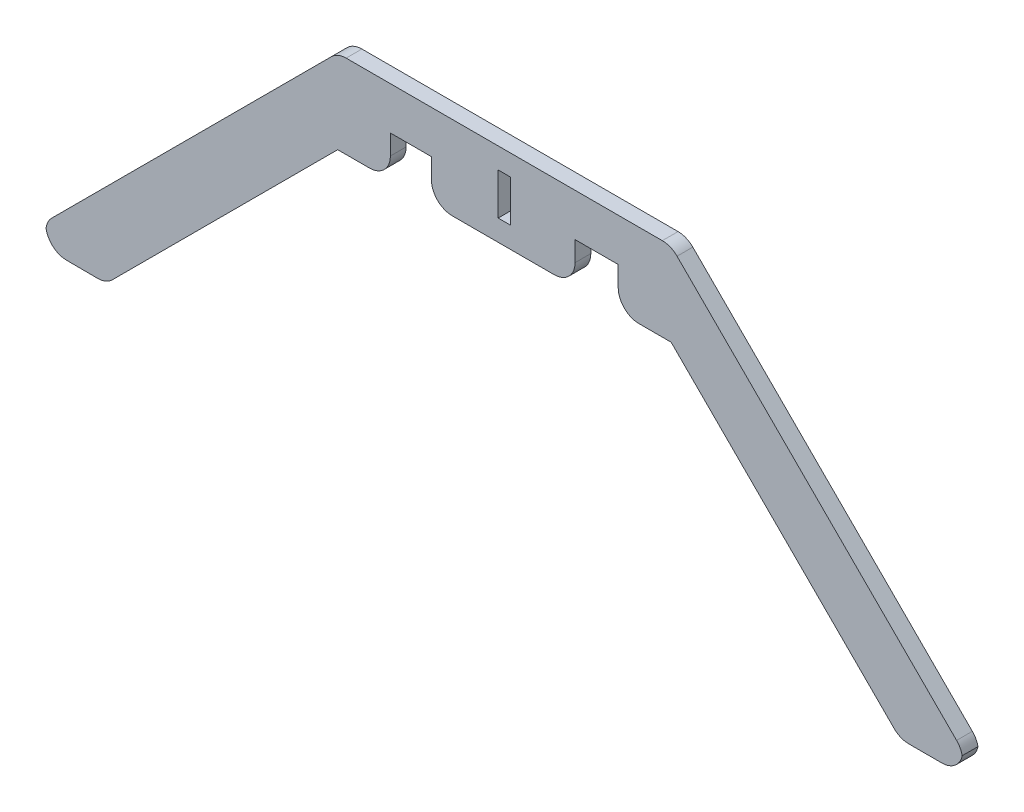
SolidWorks part; units mm, degrees
ref_plane "Front Plane" through (0, 0, 0) normal (0, 0, 1) x (1, 0, 0)
ref_plane "Top Plane" through (0, 0, 0) normal (0, 1, 0) x (1, 0, 0)
ref_plane "Right Plane" through (0, 0, 0) normal (1, 0, 0) x (0, 0, -1)
other "Center of Mass"
sketch "Sketch1" plane through (0, 0, 0) normal (0, 0, 1) x (1, 0, 0)
  line L1 (0, 0) -> (279.4, 0)
  line L2 (0, 0) -> (0, 254)
  line L3 (0, 254) -> (279.4, 254)
  line L4 (279.4, 0) -> (279.4, 254)
  line L5 (0, 0) -> (279.4, 254) construction
  line L6 (0, 254) -> (279.4, 0) construction
  point P4 (139.7, 127)
  dimension "D1" = 279.4
  dimension "D2" = 254
extrude "Boss-Extrude1" add sketch "Sketch1" along normal blind 4.8
ref_plane "Plane1" through (139.7, 0, 0) normal (-1, 0, 0) x (0, 0, 1)
sketch "Sketch4" plane through (0, 0, 0) normal (0, 0, -1) x (-1, 0, 0)
  line L16 (0.6384, 79.1893) -> (-88.9, 168.7277)
  line L17 (-88.9, 168.7277) -> (-190.5, 168.7277)
  line L18 (-190.5, 168.7277) -> (-279.4, 79.8277)
  line L20 (-18.4112, 72.7241) -> (-88.9574, 143.2703)
  line L21 (0.6384, 72.8393) -> (-18.4112, 72.7241)
  line L22 (-88.9574, 143.2703) -> (-190.5574, 143.2703)
  line L23 (-279.4, 73.4777) -> (-260.35, 73.4777)
  line L24 (-190.5574, 143.2703) -> (-260.35, 73.4777)
  line L26 (0.6384, 79.1893) -> (0.6384, 72.8393)
  line L27 (-279.4, 79.8277) -> (-279.4, 73.4777)
  line L29 (-88.9, 156.0277) -> (-190.5, 156.0277) construction
  line L30 (-141.6624, 162.3777) -> (-137.8524, 162.3777)
  line L35 (-141.6624, 162.3777) -> (-141.6624, 149.6777)
  line L36 (-141.6624, 149.6777) -> (-137.8524, 149.6777)
  line L37 (-137.8524, 162.3777) -> (-137.8524, 149.6777)
  line L38 (-105.0011, 143.2703) -> (-117.5137, 143.2703)
  line L39 (-105.0011, 143.2703) -> (-105.0011, 155.7128)
  line L40 (-105.0011, 155.7128) -> (-117.5137, 155.7128)
  line L41 (-117.5137, 143.2703) -> (-117.5137, 155.7128)
  line L42 (-105.0011, 143.2703) -> (-117.5137, 155.7128) construction
  line L43 (-105.0011, 155.7128) -> (-117.5137, 143.2703) construction
  line L44 (-161.2832, 143.2703) -> (-174.4316, 143.2703)
  line L45 (-161.2832, 143.2703) -> (-161.2832, 155.7128)
  line L46 (-161.2832, 155.7128) -> (-174.4316, 155.7128)
  line L47 (-174.4316, 143.2703) -> (-174.4316, 155.7128)
  line L48 (-161.2832, 143.2703) -> (-174.4316, 155.7128) construction
  line L49 (-161.2832, 155.7128) -> (-174.4316, 143.2703) construction
  line L50 (-141.6624, 162.3777) -> (-137.8524, 149.6777) construction
  line L51 (-141.6624, 149.6777) -> (-137.8524, 162.3777) construction
  point P14 (-139.7574, 156.0277)
  point P16 (-139.7574, 149.6777)
  point P22 (-111.2574, 149.4915)
  point P27 (-167.8574, 149.4915)
  point P32 (-167.8574, 149.6203)
  point P33 (-111.2574, 149.6203)
  line M1 (0, 0) -> (0, 254)
  line M2 (0, 254) -> (-279.4, 254)
  line M3 (-279.4, 254) -> (-279.4, 0)
  line M4 (-279.4, 0) -> (0, 0)
  dimension "D1" = 3.81
  dimension "D2" = 6.35
  dimension "D3" = 50.8
  dimension "D4" = 0
  dimension "D5" = 0
  dimension "D6" = 0
  dimension "D7" = 6.35
extrude "Cut-Extrude1" cut sketch "Sketch4" against normal through all contours L22 L24 L23 L21 L20 M3 M4 M1 | L18 L17 L16 M1 M2 M3 | L47 L22 L45 L46 | L37 L30 L35 L36 | L41 L22 L39 L40 region at (139.7, 193.3622, 0) region at (139.7737, 61.3631, 0) region at (111.2574, 149.4915, 0) region at (167.8574, 149.4915, 0) region at (139.7574, 156.0277, 0)
fillet "Fillet1" radius 6.35 12 edges at (0, 72.8354, 2.4) (0, 79.8277, 2.4) (88.9, 168.7277, 2.4) (190.5, 168.7277, 2.4) (279.4, 79.8277, 2.4) (279.4, 73.4777, 2.4) (105.0011, 143.2703, 2.4) (117.5137, 143.2703, 2.4) (161.2832, 143.2703, 2.4) (174.4316, 143.2703, 2.4) (260.35, 73.4777, 2.4) (18.4112, 72.7241, 2.4)
equation "\"MDF\"= 4.8mm"
equation "\"Foamcore\"= 4.6mm"
equation "\"PCB\" = 1.6mm"
equation "\"GMaterial\"= \"MDF\""
equation "\"BaseWidth\" = 10in"
equation "\"SkidLength\" = 1in"
equation "\"SkidClearance\" = 0.4in"
equation "\"MotorMountLength\" = 2in"
equation "\"MotorMountWidth\" = \"GMaterial\""
equation "\"MotorMountHeight\" = 2.25in"
equation "\"UnoStackWidth\" = 77.4mm"
equation "\"UnoStackLength\" = 79.8mm"
equation "\"UnoStackHeight\" = 34.2mm"
equation "\"TallHexRiserHeight\" = 22.2mm"
equation "\"PingPongBallSize\" = 40mm"
equation "\"BarrelLength\" = 9in"
equation "\"BarrelSize\" = \"PingPongBallSize\""
equation "\"PlatformLength\" = 4in"
equation "\"PlatformWidth\" = 6in"
equation "\"WheelWidth\"= 26mm"
equation "\"WheelDiameter\"=2.99213"
equation "\"ServoMountHeight\"=2.49223"
equation "\"ServoGearHeight\" = 0.95330261in"
equation "\"ServoMountLength\"= 1.53774"
equation "\"PivotHoleRadius\"= 0.616358"
equation "\"PlatformMountHeight\" = 3.19"
equation "\"TensionOffSet\"= .3mm"
equation "\"MotorMountWedge\"=0.333333"
equation "\"LaserCutterOffset\"= .3mm"
equation "\"D1@Boss-Extrude1\"=\"GMaterial\""
equation "\"BumperWidth\"=11"
equation "\"D1@Sketch1\"=\"BumperWidth\""
equation "\"D2@Sketch1\"=\"BaseWidth\""
